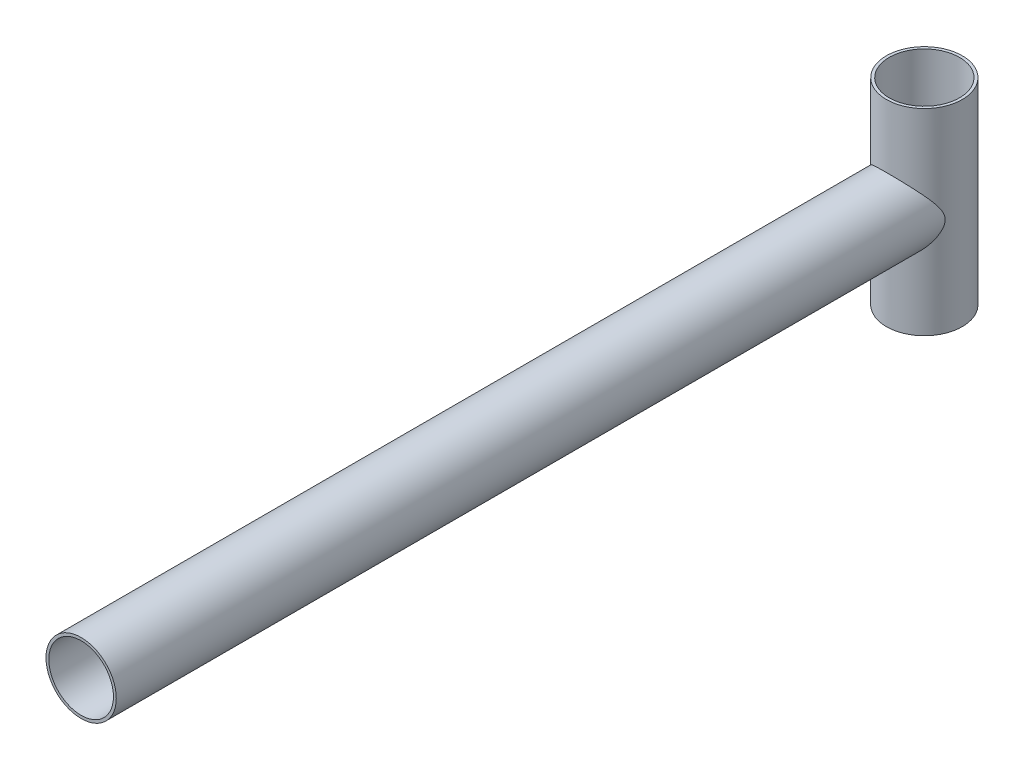
SolidWorks part; units mm, degrees
ref_plane "Front Plane" through (0, 0, 0) normal (0, 0, 1) x (1, 0, 0)
ref_plane "Top Plane" through (0, 0, 0) normal (0, 1, 0) x (1, 0, 0)
ref_plane "Right Plane" through (0, 0, 0) normal (1, 0, 0) x (0, 0, -1)
sketch "Sketch1" plane through (0, 0, 0) normal (0, 1, 0) x (1, 0, 0)
  circle A0 centre (0, 0) radius 13.5
  dimension "D1" = 27
extrude "Boss-Extrude1" add sketch "Sketch1" along normal mid plane 70
sketch "Sketch2" plane through (0, 0, 0) normal (0, 0, 1) x (1, 0, 0)
  circle A0 centre (0, 0) radius 12.5
  dimension "D1" = 25
extrude "Boss-Extrude2" add sketch "Sketch2" along normal blind 300
shell "Shell1" thickness 1 removed face at (0, 35, 13.5) removed face at (12.5, 0, 300) removed face at (0, -35, 13.5)
